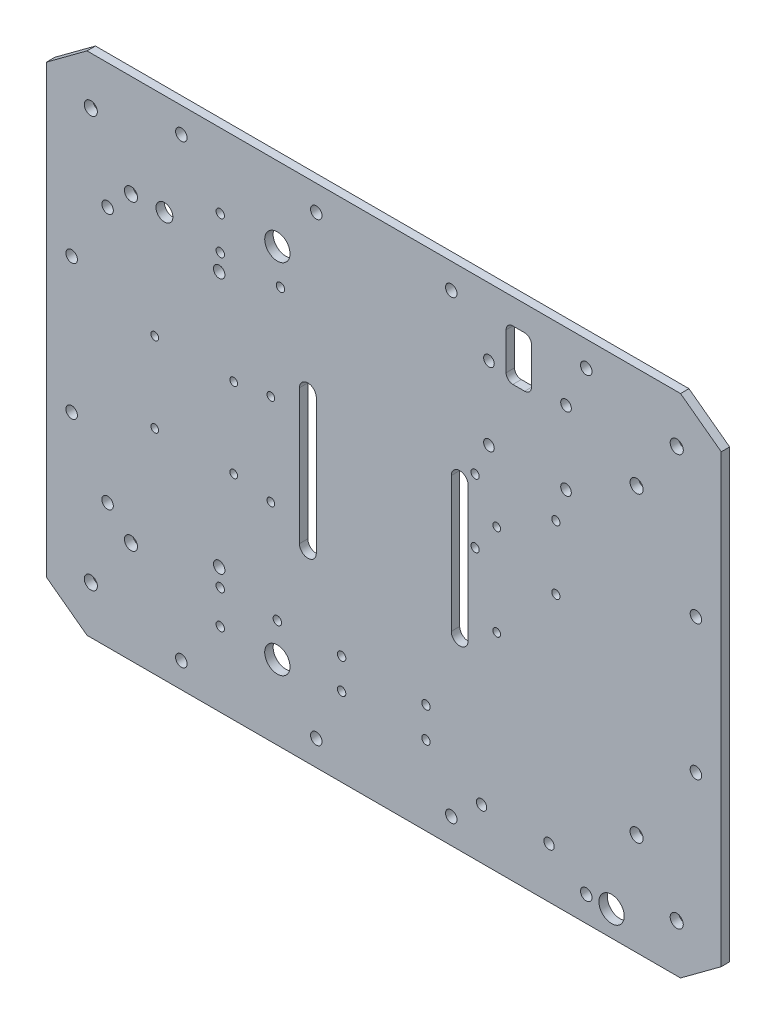
SolidWorks part; units mm, degrees
material "Thornel Mat VMA"
ref_plane "Front Plane" through (0, 0, 0) normal (0, 0, 1) x (1, 0, 0)
ref_plane "Top Plane" through (0, 0, 0) normal (0, 1, 0) x (1, 0, 0)
ref_plane "Right Plane" through (0, 0, 0) normal (1, 0, 0) x (0, 0, -1)
sketch "Sketch1" plane through (0, 0, 0) normal (0, 0, 1) x (1, 0, 0)
  line L0 (-127, 0) -> (127, 0) construction
  line L1 (0, -95.25) -> (0, 95.25) construction
  line L2 (-107.95, 0) -> (-107.95, 41.011) construction
  line L3 (-107.95, 41.011) -> (-95.25, 41.011) construction
  line L4 (-95.25, 41.011) -> (-79.9365, 52.3423) construction
  line L5 (-79.9365, 52.3423) -> (-79.9365, 76.2) construction
  line L6 (-79.9365, 76.2) -> (0, 76.2) construction
  line L7 (-95.25, 41.011) -> (-127, 83.9186) construction
  line L8 (-79.9365, 52.3423) -> (-111.6865, 95.25) construction
  line L9 (-111.6865, -95.25) -> (-127, -83.9186)
  line L10 (111.6865, -95.25) -> (127, -83.9186)
  line L11 (111.6865, 95.25) -> (127, 83.9186)
  line L12 (-87.5933, 46.6767) -> (-95.1475, 56.8856) construction
  line L13 (-95.1475, 56.8856) -> (-110.256, 77.3036) construction
  line L24 (127, -83.9186) -> (127, 83.9186)
  line L26 (111.6865, 95.25) -> (-111.6865, 95.25)
  line L27 (-111.6865, 95.25) -> (-127, 83.9186)
  line L28 (-127, 83.9186) -> (-127, -83.9186)
  line L30 (-111.6865, -95.25) -> (111.6865, -95.25)
  circle A0 centre (-95.1475, 56.8856) radius 2.4638
  circle A1 centre (-110.256, 77.3036) radius 2.4638
  circle A2 centre (110.256, 77.3036) radius 2.4638
  circle A3 centre (95.1475, 56.8856) radius 2.4638
  circle A4 centre (-110.256, -77.3036) radius 2.4638
  circle A5 centre (-95.1475, -56.8856) radius 2.4638
  circle A6 centre (110.256, -77.3036) radius 2.4638
  circle A7 centre (95.1475, -56.8856) radius 2.4638
  point P12 (0, 0)
  dimension "D1" = 190.5
  dimension "D2" = 254
  dimension "D3" = 19.05
  dimension "D4" = 19.05
  dimension "D5" = 12.7
  dimension "D6" = 19.05
  dimension "D7" = 143.5
  dimension "D8" = 12.7
  dimension "D9" = 25.4
extrude "Boss-Extrude1" add sketch "Sketch1" along normal blind 3.175
sketch "Sketch3" plane through (0, 0, 3.175) normal (0, 0, 1) x (1, 0, 0)
  line L0 (0, 95.25) -> (0, -95.25) construction
  line L1 (111.6865, 95.25) -> (-111.6865, 95.25) construction
  line L2 (-111.6865, -95.25) -> (111.6865, -95.25) construction
  line L3 (127, 0) -> (-127, 0) construction
  line L4 (127, -83.9186) -> (127, 83.9186) construction
  line L5 (-127, 83.9186) -> (-127, -83.9186) construction
  circle A0 centre (-15.875, -65.5603) radius 1.5875
  circle A1 centre (15.875, -65.5603) radius 1.5875
  circle A2 centre (-15.875, -54.1303) radius 1.5875
  circle A3 centre (15.875, -54.1303) radius 1.5875
  dimension "D2" = 11.43
  dimension "D1" = 15.875
sketch "Sketch5" plane through (0, 0, 0) normal (0, 0, -1) x (-1, 0, 0)
  line L0 (-127, 0) -> (127, 0) construction
  line L1 (107.95, 52.136) -> (57.9501, 52.136) construction
  line L2 (107.95, 52.136) -> (107.95, -34.864) construction
  line L3 (107.95, -34.864) -> (57.9501, -34.864) construction
  line L4 (57.9501, 52.136) -> (57.9501, -34.864) construction
  line L5 (89.4966, 18.0341) -> (89.4966, -18.0339)
  line L6 (67.8946, 95.25) -> (67.8946, -95.25) construction
  line L7 (111.6865, -95.25) -> (-111.6865, -95.25) construction
  line L8 (0, 64.0679) -> (0, -49.8393) construction
  line L9 (-42.5, 17.2) -> (42.5, 17.2) construction
  line L10 (-42.5, 17.2) -> (-42.5, -17.2) construction
  line L11 (-42.5, -17.2) -> (42.5, -17.2) construction
  line L12 (42.5, 17.2) -> (42.5, -17.2) construction
  line L13 (-42.5, 17.2) -> (42.5, -17.2) construction
  line L14 (-42.5, -17.2) -> (42.5, 17.2) construction
  line L15 (46.8402, 60.96) -> (31.75, 60.96) construction
  line L16 (61.5446, -67.31) -> (-87.4336, -67.31) construction
  line L17 (-127, -83.9186) -> (-127, 83.9186) construction
  line L18 (40.0554, 67.31) -> (18.5661, 67.31) construction
  line L19 (-28.575, 25.4) -> (-28.575, -25.4) construction
  line L20 (127, 83.9186) -> (127, -83.9186) construction
  line L21 (-127, -83.9186) -> (-127, 83.9186) construction
  line L22 (-50.8, 76.2) -> (82.55, 76.2) construction
  line L23 (82.55, 76.2) -> (82.55, 57.216) construction
  line L25 (82.55, -68.4098) -> (82.55, 57.216) construction
  line L26 (127, 0) -> (-127, 0) construction
  line L27 (82.95, 0) -> (82.9501, -8419.0368) construction
  line L28 (-25.4, 25.4) -> (-25.4, -25.4)
  line L29 (-31.75, 25.4) -> (-31.75, -25.4)
  line L30 (28.575, 25.4) -> (28.575, -25.4) construction
  line L31 (25.4, 25.4) -> (25.4, -25.4)
  line L32 (31.75, 25.4) -> (31.75, -25.4)
  line L33 (71.3384, 0) -> (71.3384, 12.3782) construction
  line L34 (53.4794, 18.0341) -> (89.4966, 18.0341)
  line L35 (53.4794, 18.0341) -> (53.4794, -18.0339)
  line L36 (53.4794, -18.0339) -> (89.4966, -18.0339)
  line L37 (-46.0375, 66.675) -> (-55.5625, 66.675)
  line L38 (-46.0375, 66.675) -> (-46.0375, 85.725)
  line L39 (-46.0375, 85.725) -> (-55.5625, 85.725)
  line L40 (-50.8, 76.2) -> (-50.8, 95.25) construction
  line L41 (-55.5625, 66.675) -> (-55.5625, 85.725)
  line L42 (-46.0375, 66.675) -> (-55.5625, 85.725) construction
  line L43 (-46.0375, 85.725) -> (-55.5625, 66.675) construction
  line L47 (-127, -83.9186) -> (-127, 83.9186) construction
  line L48 (-111.6865, 95.25) -> (111.6865, 95.25) construction
  circle A0 centre (61.5446, -54.61) radius 1.5875
  circle A1 centre (61.5446, -67.31) radius 1.5875
  circle A2 centre (82.55, 57.216) radius 3.175
  circle A3 centre (-85.725, -85.725) radius 4.7625
  circle A4 centre (61.5446, 54.61) radius 1.5875
  circle A7 centre (40.0554, -67.31) radius 4.7625
  circle A8 centre (61.5446, 67.31) radius 1.5875
  circle A10 centre (40.0554, 67.31) radius 4.7625
  circle A12 centre (61.9506, 48.1355) radius 2.159
  circle A13 centre (103.9495, 48.1355) radius 2.159
  circle A14 centre (61.9506, -48.1355) radius 2.159
  circle A15 centre (103.9495, -48.1355) radius 2.159
  circle A17 centre (38.8861, 54.61) radius 1.5875
  circle A19 centre (40.0554, -54.61) radius 1.5875
  arc A20 (-25.4, 25.4) -> (-31.75, 25.4) centre (-28.575, 25.4) ccw
  arc A21 (-31.75, -25.4) -> (-25.4, -25.4) centre (-28.575, -25.4) ccw
  arc A22 (25.4, 25.4) -> (31.75, 25.4) centre (28.575, 25.4) cw
  arc A23 (31.75, -25.4) -> (25.4, -25.4) centre (28.575, -25.4) cw
  circle A24 centre (56.4794, 15.0341) radius 1.4478
  circle A25 centre (56.4794, -15.0341) radius 1.4478
  circle A26 centre (86.1974, -15.0341) radius 1.4478
  circle A27 centre (86.1974, 15.0341) radius 1.4478
  circle A28 centre (-42.5, 17.2) radius 1.4542
  circle A29 centre (-42.5, -17.2) radius 1.4541
  circle A30 centre (42.5, -17.2) radius 1.4541
  circle A31 centre (42.5, 17.2) radius 1.4542
  point P0 (82.95, 0)
  point P9 (0, 0)
  point P77 (-28.575, 0)
  point P84 (28.575, 0)
  point P89 (71.3384, 0)
  dimension "D10" = 6.35
  dimension "D15" = 2.9997
  dimension "D17" = 41.275
  dimension "D18" = 41.9989
  dimension "D21" = 47.1145
  dimension "D22" = 76.2
  dimension "D25" = 4.0005
  dimension "D45" = 2.8956
  dimension "D9" = 9.525
  dimension "D13" = 14.859
  dimension "D14" = 3
  dimension "D20" = 9.525
  dimension "D8" = 9.525
  dimension "D19" = 19.05
  dimension "D16" = 9.525
  dimension "D1" = 87.0001
  dimension "D2" = 49.9999
  dimension "D4" = 34.4
  dimension "D5" = 85
  dimension "D6" = 6.35
  dimension "D7" = 19.05
  dimension "D11" = 5.08
  dimension "D12" = 25.4
  dimension "D24" = 19.05
  dimension "D26" = 4.0005
  dimension "D38" = 50.8
  dimension "D39" = 6.35
  dimension "D40" = 28.575
  dimension "D41" = 36.0172
  dimension "D42" = 36.068
  dimension "D44" = 3
extrude "Cut-Extrude2" cut sketch "Sketch5" against normal through all contours A2 | A14 | A15 | A13 | A12 | L29 A21 L28 A20 | A23 L4 A22 L31 | A23 L32 A22 L4 | A27 | A24 | A25 | A26
sketch "Sketch6" plane through (0, 0, 0) normal (0, 0, -1) x (-1, 0, 0)
  line L0 (0, 0) -> (-135.1326, 0) construction
  line L1 (0, 0) -> (0, -95.25) construction
  line L2 (111.6865, -95.25) -> (-111.6865, -95.25) construction
  line L3 (-76.2, -95.25) -> (-76.2, -85.725) construction
  line L4 (117.475, 0) -> (117.475, -25.4) construction
  line L5 (127, 0) -> (-127, 0) construction
  line L6 (127, 83.9186) -> (127, -83.9186) construction
  circle A0 centre (-76.2, -85.725) radius 2.159
  circle A1 centre (-25.4, -85.725) radius 2.159
  circle A2 centre (25.4, -85.725) radius 2.159
  circle A3 centre (76.2, -85.725) radius 2.159
  circle A4 centre (76.2, 85.725) radius 2.159
  circle A5 centre (25.4, 85.725) radius 2.159
  circle A6 centre (-25.4, 85.725) radius 2.159
  circle A7 centre (-76.2, 85.725) radius 2.159
  circle A8 centre (117.475, -25.4) radius 2.159
  circle A9 centre (117.475, 25.4) radius 2.159
  circle A10 centre (-117.475, 25.4) radius 2.159
  circle A11 centre (-117.475, -25.4) radius 2.159
  dimension "D2" = 9.525
  dimension "D3" = 76.2
  dimension "D5" = 9.525
  dimension "D6" = 25.4
  dimension "D4" = 4
extrude "Cut-Extrude3" cut sketch "Sketch6" against normal through all
extrude "Cut-Extrude4" cut sketch "Sketch5<3>" against normal through all contours A28 | A29 | A31 | A30
sketch "Sketch5<3>" plane through (0, 0, 0) normal (0, 0, -1) x (-1, 0, 0) same geometry as "Sketch5"
extrude "Cut-Extrude5" cut sketch "Sketch5<4>" against normal through all contours A3 | A10 | A8 | A4 | A0 | A1 | A7 region at (85.725, -85.725, 0)
sketch "Sketch5<4>" plane through (0, 0, 0) normal (0, 0, -1) x (-1, 0, 0) same geometry as "Sketch5"
extrude "Cut-Extrude6" cut sketch "Sketch5<5>" against normal blind 2.54 contours A17
sketch "Sketch5<5>" plane through (0, 0, 0) normal (0, 0, -1) x (-1, 0, 0) same geometry as "Sketch5"
extrude "Cut-Extrude7" cut sketch "Sketch5<6>" against normal through all contours A17
sketch "Sketch5<6>" plane through (0, 0, 0) normal (0, 0, -1) x (-1, 0, 0) same geometry as "Sketch5"
extrude "Cut-Extrude8" cut sketch "Sketch5<7>" against normal blind 2.54 and the other way blind 7.62 contours L41 L37 L38 L39 | A19
sketch "Sketch5<7>" plane through (0, 0, 0) normal (0, 0, -1) x (-1, 0, 0) same geometry as "Sketch5"
extrude "Cut-Extrude9" cut sketch "Sketch5<9>" against normal through all contours A19
sketch "Sketch5<9>" plane through (0, 0, 0) normal (0, 0, -1) x (-1, 0, 0) same geometry as "Sketch5"
extrude "Cut-Extrude17" cut sketch "Sketch5<15>" against normal through all both and the other way through all contours L39 L41 L37 L38
sketch "Sketch5<15>" plane through (0, 0, 0) normal (0, 0, -1) x (-1, 0, 0) same geometry as "Sketch5"
fillet "Fillet1" radius 2.54 1 edges at (55.5625, 85.725, 1.5875) type face fillet first side face at (55.5625, 76.2, 1.5875) second side face at (50.8, 85.725, 1.5875)
fillet "Fillet2" radius 2.54 1 edges at (46.0375, 85.725, 1.5875) type face fillet first side face at (49.53, 85.725, 1.5875) second side face at (46.0375, 76.2, 1.5875)
sketch "Sketch2" plane through (0, 0, 3.175) normal (0, 0, 1) x (1, 0, 0)
  line L0 (-127, 0) -> (127, 0) construction
  line L1 (-127, 83.9186) -> (-127, -83.9186) construction
  line L2 (127, -83.9186) -> (127, 83.9186) construction
  line L3 (49.4994, 93.2242) -> (49.4994, -65.0875) construction
  line L5 (-111.6865, -95.25) -> (111.6865, -95.25) construction
  circle A1 centre (62.1994, -76.2) radius 1.9431
  circle A3 centre (36.7994, -76.2) radius 1.9431
  point P10 (0, 0)
  point P13 (0, 0)
  point P14 (-2.0372, 61.4579)
  point P15 (0, 0)
  point P18 (0, 93.2242)
  point P19 (0, 0)
  point P20 (49.4994, -56.0052)
  dimension "D1" = 12.7
  dimension "D3" = 19.05
  dimension "D2" = 12.7
extrude "Cut-Extrude20" cut sketch "Sketch2" against normal through all
fillet "Fillet3" radius 2.54 1 edges at (46.0375, 66.675, 1.5875) type face fillet first side face at (50.8, 66.675, 1.5875) second side face at (46.0375, 74.93, 1.5875)
fillet "Fillet4" radius 2.54 1 edges at (55.5625, 66.675, 1.5875) type face fillet first side face at (52.07, 66.675, 1.5875) second side face at (55.5625, 74.93, 1.5875)
sketch "Sketch9" plane through (0, 0, 3.175) normal (0, 0, 1) x (1, 0, 0)
  line L0 (127, -83.9186) -> (127, 83.9186) construction
  line L1 (34.37, 30.35) -> (64.77, 30.35) construction
  line L2 (34.37, 30.35) -> (34.37, 6.35) construction
  line L3 (34.37, 6.35) -> (64.77, 6.35) construction
  line L4 (64.77, 30.35) -> (64.77, 6.35) construction
  line L5 (-111.6865, -95.25) -> (111.6865, -95.25) construction
  line L6 (127, -83.9186) -> (127, 83.9186) construction
  line L7 (68.58, 69.85) -> (39.58, 69.85) construction
  line L8 (68.58, 69.85) -> (68.58, 42.35) construction
  line L9 (68.58, 42.35) -> (39.58, 42.35) construction
  line L10 (39.58, 69.85) -> (39.58, 42.35) construction
  line L11 (111.6865, 95.25) -> (-111.6865, 95.25) construction
  line L12 (127, 0) -> (0, 0) construction
  circle A0 centre (34.37, 30.35) radius 1.55
  circle A1 centre (64.77, 30.35) radius 1.55
  circle A2 centre (64.77, 6.35) radius 1.55
  circle A3 centre (34.37, 6.35) radius 1.55
  circle A4 centre (68.58, 69.85) radius 2
  circle A5 centre (39.58, 69.85) radius 2
  circle A6 centre (39.58, 42.35) radius 2
  circle A7 centre (68.58, 42.35) radius 2
  dimension "D1" = 3.1
  dimension "D6" = 4
  dimension "D2" = 24
  dimension "D3" = 30.4
  dimension "D4" = 62.23
  dimension "D5" = 101.6
  dimension "D7" = 29
  dimension "D8" = 27.5
  dimension "D9" = 58.42
  dimension "D10" = 25.4
extrude "Cut-Extrude18" cut sketch "Sketch9" against normal through all
extrude "Cut-Extrude19" cut sketch "Sketch3" against normal blind 976.122
